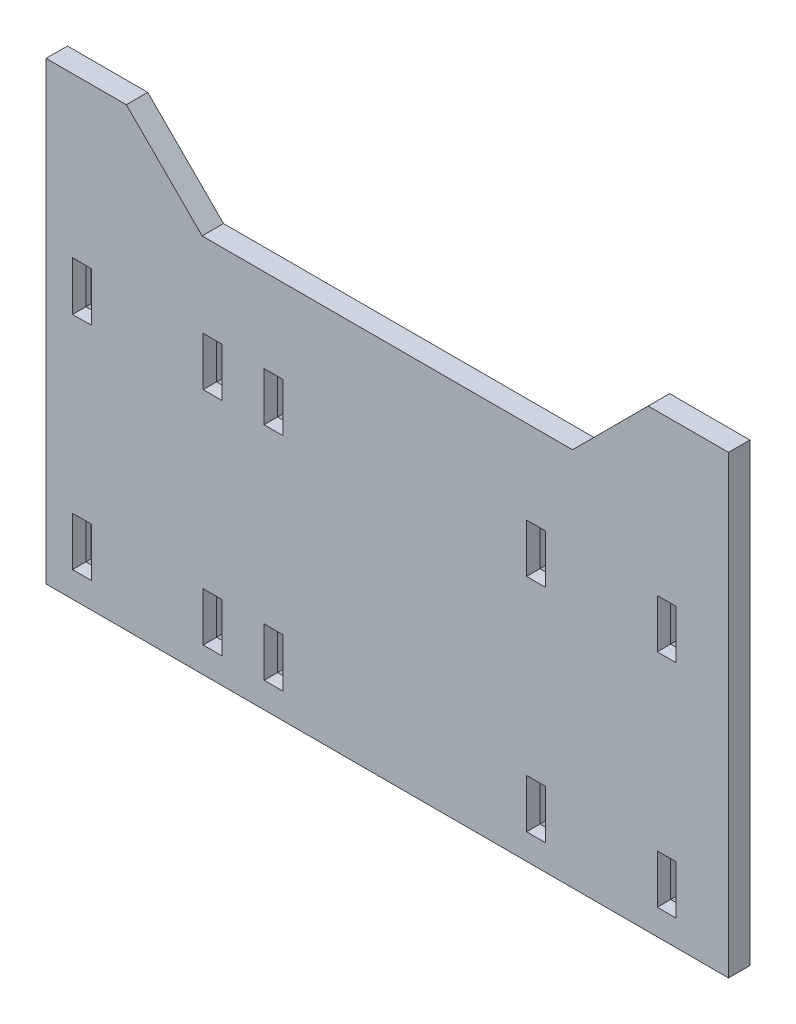
SolidWorks part; units mm, degrees
ref_plane "Front Plane" through (0, 0, 0) normal (0, 0, 1) x (1, 0, 0)
ref_plane "Top Plane" through (0, 0, 0) normal (0, 1, 0) x (1, 0, 0)
ref_plane "Right Plane" through (0, 0, 0) normal (1, 0, 0) x (0, 0, -1)
sketch "Sketch1" plane through (0, 0, 0) normal (0, 0, 1) x (1, 0, 0)
  line L6 (-34.3851, 25.207) -> (-30.8551, 25.207)
  line L7 (26.0149, 25.207) -> (29.5449, 25.207)
  line L8 (26.0149, 25.207) -> (26.0149, 16.093)
  line L9 (26.0149, 16.093) -> (29.5449, 16.093)
  line L10 (29.5449, 25.207) -> (29.5449, 16.093)
  line L12 (26.0149, -16.093) -> (29.5449, -16.093)
  line L13 (26.0149, -25.207) -> (26.0149, -16.093)
  line L14 (29.5449, -25.207) -> (29.5449, -16.093)
  line L15 (26.0149, -25.207) -> (29.5449, -25.207)
  line L16 (-19.4551, 25.207) -> (-22.9851, 25.1844)
  line L17 (-19.4551, 25.207) -> (-19.4406, 16.093)
  line L18 (-22.9851, 25.1844) -> (-22.9996, 16.1156)
  line L19 (-19.4406, 16.093) -> (-22.9996, 16.1156)
  line L20 (-19.4551, -16.093) -> (-22.9851, -16.093)
  line L21 (-19.4551, -25.207) -> (-19.4551, -16.093)
  line L22 (-22.9851, -25.207) -> (-22.9851, -16.093)
  line L23 (-19.4551, -25.207) -> (-22.9851, -25.207)
  line L39 (50.4149, 25.207) -> (53.9449, 25.207)
  line L40 (50.4149, 25.207) -> (50.4149, 16.093)
  line L41 (50.4149, 16.093) -> (53.9449, 16.093)
  line L42 (53.9449, 25.207) -> (53.9449, 16.093)
  line L43 (50.4149, -16.093) -> (53.9449, -16.093)
  line L44 (50.4149, -16.093) -> (50.4149, -25.207)
  line L45 (50.4149, -25.207) -> (53.9449, -25.207)
  line L46 (53.9449, -16.093) -> (53.9449, -25.207)
  line L47 (-34.3851, 25.207) -> (-34.3851, 16.093)
  line L48 (-34.3851, 16.093) -> (-30.8551, 16.093)
  line L49 (-30.8551, 25.207) -> (-30.8551, 16.093)
  line L50 (-34.3851, -16.093) -> (-30.8551, -16.093)
  line L51 (-34.3851, -16.093) -> (-34.3851, -25.207)
  line L52 (-34.3851, -25.207) -> (-30.8551, -25.207)
  line L53 (-30.8551, -16.093) -> (-30.8551, -25.207)
  line L60 (-58.785, 25.25) -> (-55.2552, 25.207)
  line L61 (-58.785, 25.25) -> (-58.785, 16.05)
  line L62 (-58.785, 16.05) -> (-55.2552, 16.093)
  line L63 (-55.2552, 25.207) -> (-55.2552, 16.093)
  line L64 (-58.7851, -16.093) -> (-55.2551, -16.093)
  line L65 (-58.7851, -16.093) -> (-58.7851, -25.207)
  line L66 (-58.7851, -25.207) -> (-55.2551, -25.207)
  line L67 (-55.2551, -16.093) -> (-55.2551, -25.207)
  line L80 (-63.7201, 30) -> (63.7201, 30)
  line L81 (63.7201, 30) -> (63.7201, -30)
  line L82 (52.1799, 25.207) -> (52.1799, 16.093) construction
  line L83 (27.7799, 16.093) -> (27.7799, 25.207) construction
  line L84 (-63.7201, 30) -> (-63.7201, -30)
  line L85 (-63.7201, -30) -> (63.7201, -30)
  line L87 (53.2799, 20.65) -> (50.4149, 20.65) construction
  line L88 (29.5449, 20.65) -> (26.0149, 20.65) construction
  line L89 (53.9449, -20.65) -> (50.4149, -20.65) construction
  line L90 (52.1799, -16.093) -> (52.1799, -25.207) construction
  line L91 (27.7799, -16.093) -> (27.7799, -25.207) construction
  line L92 (29.5449, -20.65) -> (26.0149, -20.65) construction
  line L93 (-19.4551, -20.65) -> (-22.9851, -20.65) construction
  line L94 (-21.2201, -16.093) -> (-21.2201, -25.207) construction
  line L95 (-32.6201, -16.093) -> (-32.6201, -25.207) construction
  line L96 (-30.8551, -20.65) -> (-34.3851, -20.65) construction
  line L97 (-55.2551, -20.65) -> (-58.7851, -20.65) construction
  line L98 (-57.0201, -16.093) -> (-57.0201, -25.207) construction
  line L99 (-57.0201, 25.2285) -> (-57.0201, 16.0715) construction
  line L100 (-32.6201, 25.207) -> (-32.6201, 16.093) construction
  line L101 (-21.2201, 25.1957) -> (-21.2201, 16.1043) construction
  line L102 (-55.2552, 20.65) -> (-58.785, 20.65) construction
  line L103 (-34.3851, 20.65) -> (-30.8551, 20.65) construction
  line L104 (-19.4479, 20.65) -> (-22.9923, 20.65) construction
  point P0 (0, 0)
  point P86 (0, 30)
  point P87 (63.7201, 0)
  dimension "D1" = 9.2
  dimension "D2" = 3.53
  dimension "D3" = 127.4402
  dimension "D4" = 60
  dimension "D7" = 11.4
  dimension "D8" = 24.4
  dimension "D5" = 27.7799
  dimension "D6" = 21.2201
  dimension "D10" = 20.65
  dimension "D11" = 20.65
  dimension "D9" = 24.4
extrude "Boss-Extrude1" add sketch "Sketch1" against normal blind 4
sketch "Sketch2" plane through (0, 0, 0) normal (0, 0, 1) x (1, 0, 0)
  line L0 (-63.7201, 30) -> (-63.7201, 55)
  line L1 (-63.7201, 55) -> (-48.7201, 55)
  line L2 (-48.7201, 55) -> (-34.578, 40.8579)
  line L7 (63.7201, 30) -> (-63.7201, 30)
  line L8 (48.7201, 55) -> (63.7201, 55)
  line L9 (63.7201, 55) -> (63.7201, 30)
  line L10 (48.7201, 55) -> (34.578, 40.8579)
  line L11 (34.578, 40.8579) -> (-34.578, 40.8579)
  line L12 (-63.7201, 30) -> (-63.7201, -30) construction
  line L14 (63.7201, -30) -> (63.7201, 30) construction
  dimension "D1" = 25
  dimension "D2" = 15
  dimension "D3" = 135
  dimension "D4" = 20
extrude "Boss-Extrude2" add sketch "Sketch2" against normal blind 4
chamfer "Chamfer1" distance 1.5 distance2 0.5 40 edges at (27.7799, 16.093, -4) (29.5449, 20.65, -4) (26.0149, 20.65, -4) (27.7799, 25.207, -4) (53.9449, 20.65, -4) (52.1799, 16.093, -4) (50.4149, 20.65, -4) (52.1799, 25.207, -4) (52.1799, -25.207, -4) (53.9449, -20.65, -4) (52.1799, -16.093, -4) (50.4149, -20.65, -4) (29.5449, -20.65, -4) (27.7799, -25.207, -4) (26.0149, -20.65, -4) (27.7799, -16.093, -4) (-21.2201, -25.207, -4) (-19.4551, -20.65, -4) (-21.2201, -16.093, -4) (-22.9851, -20.65, -4) (-30.8551, -20.65, -4) (-32.6201, -25.207, -4) (-34.3851, -20.65, -4) (-32.6201, -16.093, -4) (-55.2551, -20.65, -4) (-57.0201, -16.093, -4) (-58.7851, -20.65, -4) (-57.0201, -25.207, -4) (-21.2201, 25.1957, -4) (-19.4479, 20.65, -4) (-21.2201, 16.1043, -4) (-22.9923, 20.65, -4) (-32.6201, 16.093, -4) (-30.8551, 20.65, -4) (-32.6201, 25.207, -4) (-34.3851, 20.65, -4) (-57.0201, 16.0715, -4) (-55.2552, 20.65, -4) (-57.0201, 25.2285, -4) (-58.785, 20.65, -4) first distance on face at (27.7799, 16.093, -2) first distance on face at (29.5449, 20.65, -2) first distance on face at (26.0149, 20.65, -2) first distance on face at (27.7799, 25.207, -2) first distance on face at (53.9449, 20.65, -2) first distance on face at (52.1799, 16.093, -2) first distance on face at (50.4149, 20.65, -2) first distance on face at (52.1799, 25.207, -2) first distance on face at (52.1799, -25.207, -2) first distance on face at (53.9449, -20.65, -2) first distance on face at (52.1799, -16.093, -2) first distance on face at (50.4149, -20.65, -2) first distance on face at (29.5449, -20.65, -2) first distance on face at (27.7799, -25.207, -2) first distance on face at (26.0149, -20.65, -2) first distance on face at (27.7799, -16.093, -2) first distance on face at (-21.2201, -25.207, -2) first distance on face at (-19.4551, -20.65, -2) first distance on face at (-21.2201, -16.093, -2) first distance on face at (-22.9851, -20.65, -2) first distance on face at (-30.8551, -20.65, -2) first distance on face at (-32.6201, -25.207, -2) first distance on face at (-34.3851, -20.65, -2) first distance on face at (-32.6201, -16.093, -2) first distance on face at (-55.2551, -20.65, -2) first distance on face at (-57.0201, -16.093, -2) first distance on face at (-58.7851, -20.65, -2) first distance on face at (-57.0201, -25.207, -2) first distance on face at (-21.2201, 25.1957, -2) first distance on face at (-19.4479, 20.65, -2) first distance on face at (-21.2201, 16.1043, -2) first distance on face at (-22.9923, 20.65, -2) first distance on face at (-32.6201, 16.093, -2) first distance on face at (-30.8551, 20.65, -2) first distance on face at (-32.6201, 25.207, -2) first distance on face at (-34.3851, 20.65, -2) first distance on face at (-57.0201, 16.0715, -2) first distance on face at (-55.2552, 20.65, -2) first distance on face at (-57.0201, 25.2285, -2) first distance on face at (-58.785, 20.65, -2)
equation "\"pin_hole_height\"=9.2"
equation "\"D1@Sketch1\"=\"pin_hole_height\""
equation "\"pin_hole_width\"=3.53"
equation "\"D2@Sketch1\"=\"pin_hole_width\""
equation "\"distancer\"=24.4"
equation "\"D9@Sketch1\"=\"distancer\""
